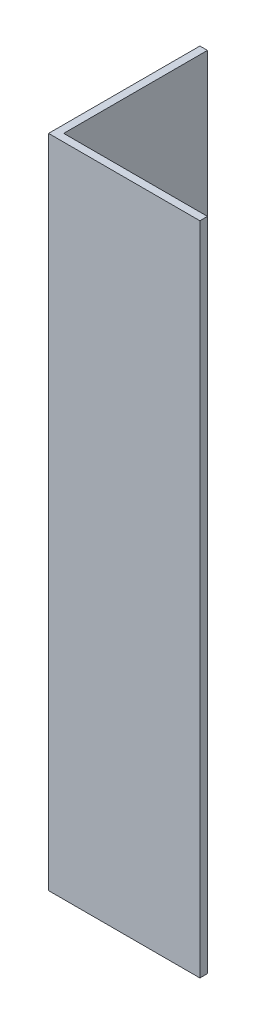
SolidWorks part; units mm, degrees
material "1060 Сплав"
ref_plane "Спереди" through (0, 0, 0) normal (0, 0, 1) x (1, 0, 0)
ref_plane "Сверху" through (0, 0, 0) normal (0, 1, 0) x (1, 0, 0)
ref_plane "Справа" through (0, 0, 0) normal (1, 0, 0) x (0, 0, -1)
sketch "Эскиз1" plane through (0, 0, 0) normal (0, 1, 0) x (1, 0, 0)
  line L0 (0, 0) -> (0, 15)
  line L1 (0, 15) -> (0.75, 15)
  line L2 (0.75, 15) -> (0.75, 0.75)
  line L3 (0.75, 0.75) -> (15, 0.75)
  line L4 (15, 0.75) -> (15, 0)
  line L5 (15, 0) -> (0, 0)
  dimension "D1" = 0.75
  dimension "D2" = 15
extrude "Бобышка-Вытянуть1" add sketch "Эскиз1" along normal blind 65
